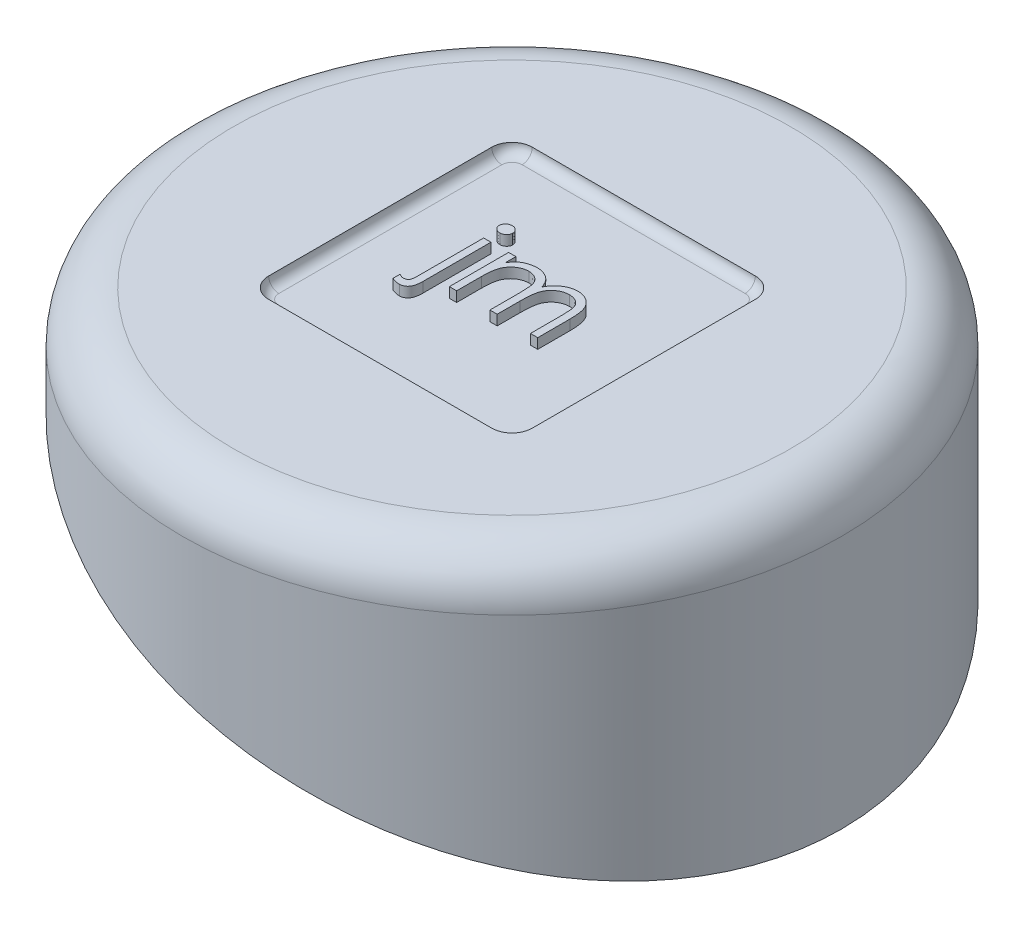
SolidWorks part; units mm, degrees
ref_plane "Front Plane" through (0, 0, 0) normal (0, 0, 1) x (1, 0, 0)
ref_plane "Top Plane" through (0, 0, 0) normal (0, 1, 0) x (1, 0, 0)
ref_plane "Right Plane" through (0, 0, 0) normal (1, 0, 0) x (0, 0, -1)
sketch "Sketch1" plane through (0, 0, 0) normal (0, 1, 0) x (1, 0, 0)
  circle A0 centre (0, 0) radius 32.5
  dimension "D1" = 65
extrude "Boss-Extrude1" add sketch "Sketch1" along normal blind 30
sketch "Sketch2" plane through (0, 0, 0) normal (0, 0, 1) x (1, 0, 0)
  line L0 (32.5, 0) -> (-32.5, 0)
  line L1 (-32.5, 0) -> (-32.5, 22.3813)
  line L2 (-32.5, 30) -> (-32.5, 0) construction
  line L3 (-32.5, 22.3813) -> (32.5, 0)
  dimension "D1" = 19
extrude "Cut-Extrude1" cut sketch "Sketch2" against normal up to body and the other way up to body separate body
fillet "Fillet1" radius 5 1 edges at (0, 30, 32.5)
shell "Shell1" thickness 2.5 removed face at (32.5, 0, 0)
sketch "Sketch3" plane through (0, 30, 0) normal (0, 1, 0) x (1, 0, 0)
  line L0 (-13, -3) -> (13, -3) construction
  line L1 (-11, -13) -> (11, -13)
  line L2 (-13, -11) -> (-13, 11)
  line L3 (-11, 13) -> (11, 13)
  line L4 (13, -11) -> (13, 11)
  line L5 (-13, -13) -> (13, 13) construction
  line L6 (-13, 13) -> (13, -13) construction
  line L7 (0, -3) -> (0, -13) construction
  arc A0 (-11, -13) -> (-13, -11) centre (-11, -11) cw
  arc A1 (11, -13) -> (13, -11) centre (11, -11) ccw
  arc A2 (11, 13) -> (13, 11) centre (11, 11) cw
  arc A3 (-13, 11) -> (-11, 13) centre (-11, 11) cw
  text T0 "jm" font "Century Gothic" height 8
  point P0 (0, 0)
  point P10 (0, -6.6363)
  point P12 (0, -4.3853)
  point P13 (0, -3.166)
  dimension "D3" = 2
  dimension "D1" = 26
  dimension "D2" = 10
extrude "Cut-Extrude2" cut sketch "Sketch3" against normal blind 1
fillet "Fillet3" radius 1 8 edges at (0, 29, -13) (12.4142, 29, -12.4142) (13, 29, 0) (12.4142, 29, 12.4142) (0, 29, 13) (-12.4142, 29, 12.4142) (-13, 29, 0) (-12.4142, 29, -12.4142)
